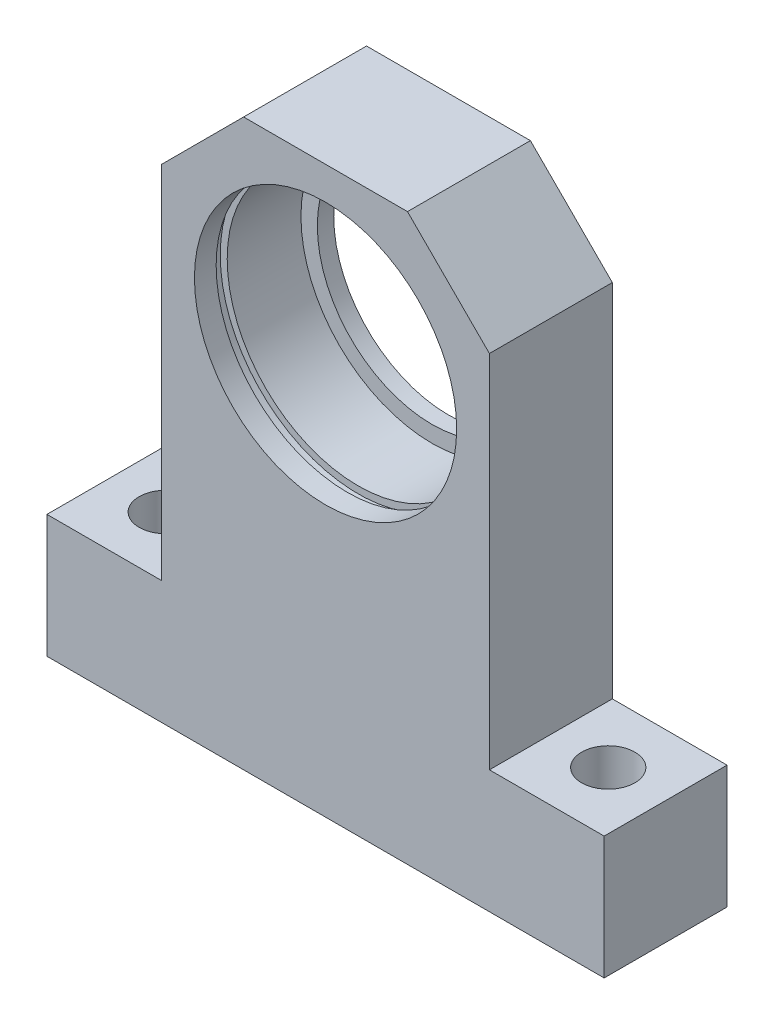
SolidWorks part; units mm, degrees
ref_plane "Front Plane" through (0, 0, 0) normal (0, 0, 1) x (1, 0, 0)
ref_plane "Top Plane" through (0, 0, 0) normal (0, 1, 0) x (1, 0, 0)
ref_plane "Right Plane" through (0, 0, 0) normal (1, 0, 0) x (0, 0, -1)
sketch "Sketch1" plane through (0, 0, 0) normal (0, 0, 1) x (1, 0, 0)
  line L0 (-20, 69) -> (20, 69)
  line L1 (20, 69) -> (20, 15)
  line L2 (20, 15) -> (34, 15)
  line L3 (34, 15) -> (34, 0)
  line L4 (34, 0) -> (-34, 0)
  line L5 (-34, 0) -> (-34, 15)
  line L6 (-34, 15) -> (-20, 15)
  line L7 (-20, 15) -> (-20, 69)
  line L8 (0, 69) -> (0, 0) construction
  point P12 (0, 49)
  dimension "L" = 68
  dimension "S" = 15
  dimension "L2" = 40
  dimension "H_s" = 49
  dimension "H" = 69
  dimension "MSM_6" = 20
extrude "Boss-Extrude1" add sketch "Sketch1" against normal blind 15
sketch "Sketch2" plane through (0, 0, 0) normal (1, 0, 0) x (0, 0, -1)
  line L0 (15, 49) -> (0, 49) construction
  line L1 (2.65, 65) -> (2.65, 65.85)
  line L2 (13, 65) -> (4, 65)
  line L3 (13, 65) -> (13, 63)
  line L4 (13, 63) -> (15, 63)
  line L5 (2.65, 65.85) -> (4, 65.85)
  line L6 (4, 65.85) -> (4, 65)
  line L7 (0, 65) -> (0, 49)
  line L8 (0, 49) -> (15, 49)
  line L9 (15, 49) -> (15, 63)
  line L11 (0, 15) -> (0, 69) construction
  line L12 (2.65, 65) -> (0, 65)
  line L13 (0, 15) -> (0, 69) construction
  line L14 (15, 15) -> (15, 69) construction
  dimension "D" = 32
  dimension "DH_s" = 28
  dimension "B" = 9
  dimension "H_s" = 49
  dimension "L1_s" = 2
  dimension "MSM_2" = 1.35
  dimension "MSM_1" = 33.7
revolve "Cut-Revolve1" cut sketch "Sketch2" angle 360 about L0
hole_wizard "Diameter Hole1" positions "Sketch4" profile "Sketch3" hole size "Ø5.5" standard "JIS" end condition through all
sketch "Sketch4" plane through (0, 15, 0) normal (0, 1, 0) x (1, 0, 0)
  line L10 (0, 0) -> (0, 15) construction
  line L11 (20, 15) -> (-20, 15) construction
  line L12 (-34, 7.5) -> (34, 7.5) construction
  line L13 (-34, 15) -> (-34, 0) construction
  line L14 (34, 15) -> (34, 0) construction
  point P0 (-27, 7.5)
  point P6 (27, 7.5)
  dimension "L1" = 54
  dimension "T/2" = 7.5
sketch "Sketch3" plane through (-27, 15, -7.5) normal (1, 0, 0) x (0, 0, 1)
  line L0 (0, 0) -> (0, 15)
  line L1 (0, 15) -> (3.25, 15)
  line L2 (3.25, 15) -> (3.25, 0)
  line L5 (3.25, 0) -> (0, 0)
  line L11 (0, 0) -> (0, 15) construction
  dimension "D1_s" = 6.5
  dimension "Thru Hole Depth" = 15
chamfer "Chamfer1" distance 10 angle 45 2 edges at (-20, 69, -7.5) (20, 69, -7.5)
chamfer "Chamfer2" [suppressed] distance 2 angle 45
